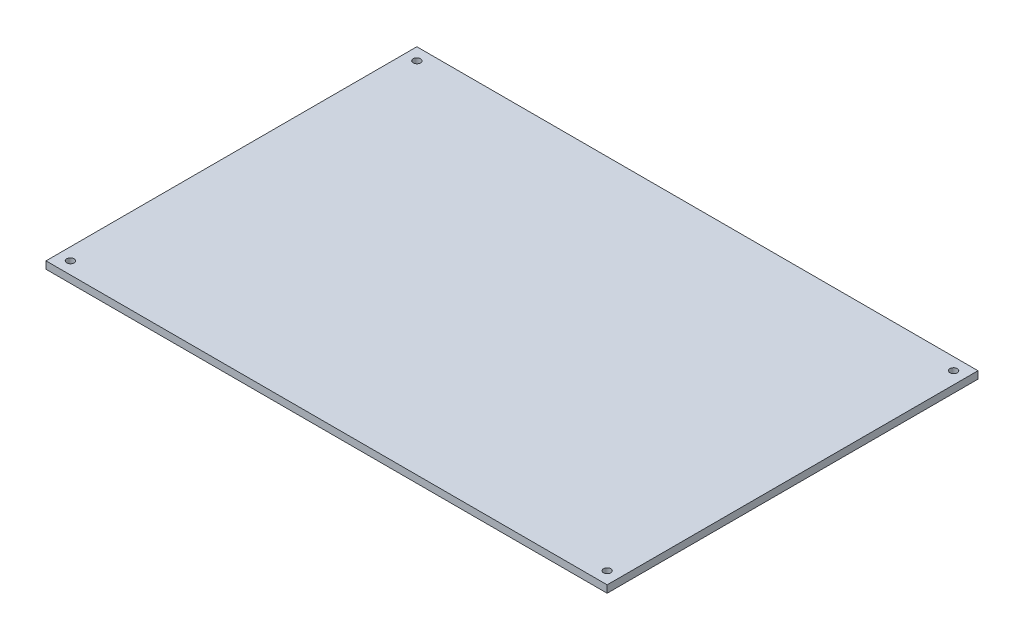
SolidWorks part; units mm, degrees
ref_plane "Спереди" through (0, 0, 0) normal (0, 0, 1) x (1, 0, 0)
ref_plane "Сверху" through (0, 0, 0) normal (0, 1, 0) x (1, 0, 0)
ref_plane "Справа" through (0, 0, 0) normal (1, 0, 0) x (0, 0, -1)
sketch "Эскиз1" plane through (0, 0, 0) normal (0, 1, 0) x (1, 0, 0)
  line L1 (-153.9032, 45.5) -> (76.0968, 45.5)
  line L2 (-153.9032, 45.5) -> (-153.9032, -106.5)
  line L3 (-153.9032, -106.5) -> (76.0968, -106.5)
  line L4 (76.0968, 45.5) -> (76.0968, -106.5)
  dimension "D1" = 230
  dimension "D2" = 152
extrude "Бобышка-Вытянуть1" add sketch "Эскиз1" along normal blind 3
sketch "Эскиз2" plane through (0, 3, 0) normal (0, 1, 0) x (1, 0, 0)
  line L0 (76.0968, 45.5) -> (-153.9032, 45.5) construction
  line L1 (-153.9032, 45.5) -> (-153.9032, -106.5) construction
  line L2 (76.0968, -106.5) -> (76.0968, 45.5) construction
  line L3 (-153.9032, -106.5) -> (76.0968, -106.5) construction
  circle A0 centre (-148.9032, 40.5) radius 1.5
  circle A1 centre (71.0968, 40.5) radius 1.5
  circle A2 centre (71.0968, -101.5) radius 1.5
  circle A3 centre (-148.9032, -101.5) radius 1.5
  dimension "D1" = 3
  dimension "D2" = 3
  dimension "D3" = 3
  dimension "D4" = 3
  dimension "D5" = 5
  dimension "D6" = 5
  dimension "D7" = 5
  dimension "D8" = 5
  dimension "D9" = 5
  dimension "D10" = 5
  dimension "D11" = 5
  dimension "D12" = 5
extrude "Вырез-Вытянуть1" cut sketch "Эскиз2" against normal blind 3
